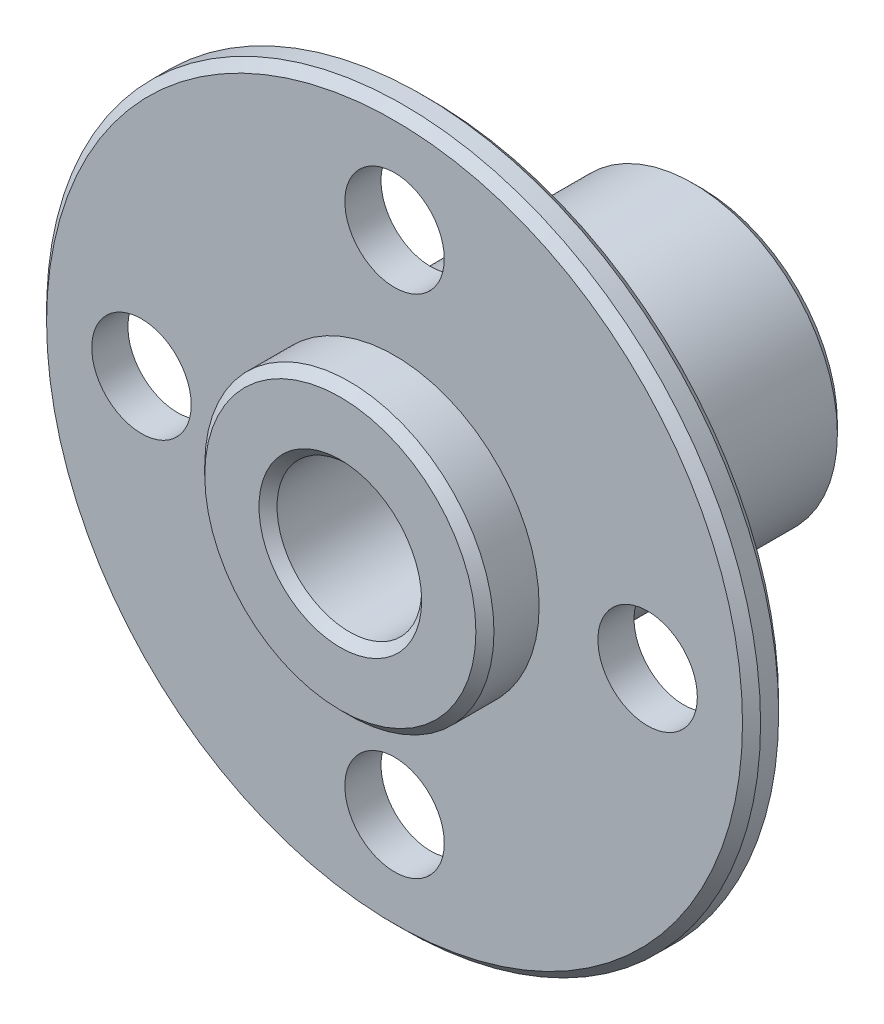
SolidWorks part; units mm, degrees
ref_plane "前视基准面" through (0, 0, 0) normal (0, 0, 1) x (1, 0, 0)
ref_plane "上视基准面" through (0, 0, 0) normal (0, 1, 0) x (1, 0, 0)
ref_plane "右视基准面" through (0, 0, 0) normal (1, 0, 0) x (0, 0, -1)
sketch "草图1" plane through (0, 0, 0) normal (0, 0, 1) x (1, 0, 0)
  circle A0 centre (0, 0) radius 19.75
  dimension "D1" = 39.5
extrude "凸台-拉伸1" add sketch "草图1" along normal blind 2
sketch "草图2" plane through (0, 0, 2) normal (0, 0, 1) x (1, 0, 0)
  circle A0 centre (0, 0) radius 8
  dimension "D1" = 16
extrude "凸台-拉伸2" add sketch "草图2" along normal blind 3
sketch "草图3" plane through (0, 0, 0) normal (0, 0, -1) x (-1, 0, 0)
  circle A0 centre (0, 0) radius 8
  dimension "D1" = 16
extrude "凸台-拉伸3" add sketch "草图3" along normal blind 15
hole_wizard "M8 螺纹孔1" positions "草图5" profile "草图4" tap size "M8" standard "GB" end condition up to next
sketch "草图5" plane through (0, 0, 5) normal (0, 0, 1) x (1, 0, 0)
  point P0 (0, 0)
sketch "草图4" plane through (0, 0, 5) normal (1, 0, 0) x (0, -1, 0)
  line L0 (0, 0) -> (0, 20)
  line L1 (0, 20) -> (4, 20)
  line L2 (4, 20) -> (4, 0)
  line L5 (4, 0) -> (0, 0)
  line L11 (0, -6.35) -> (0, 107.95) construction
  dimension "螺纹线主直径" = 8
  dimension "通孔螺纹孔钻头深度" = 20
hole_wizard "Ø5.5 (5.5) 直径孔1" positions "草图7" profile "草图6" hole size "Ø5.5" standard "GB" end condition up to next
sketch "草图7" plane through (0, 0, 2) normal (0, 0, 1) x (1, 0, 0)
  line L0 (0, 0) -> (0, 23.029) construction
  line L2 (0, 0) -> (0, -23.241) construction
  line L5 (-23.9824, 0) -> (0, 0) construction
  line L7 (0, 0) -> (25.8377, 0) construction
  circle A0 centre (0, 0) radius 14 construction
  point P0 (0, 14)
  point P1 (0, -14)
  point P3 (-14, 0)
  point P5 (14, 0)
  dimension "D1" = 28
sketch "草图6" plane through (0, 14, 2) normal (1, 0, 0) x (0, -1, 0)
  line L0 (0, 0) -> (0, 2)
  line L1 (0, 2) -> (2.75, 2)
  line L2 (2.75, 2) -> (2.75, 0)
  line L5 (2.75, 0) -> (0, 0)
  line L11 (0, -6.35) -> (0, 107.95) construction
  dimension "通孔孔直径" = 5.5
  dimension "通孔孔深度" = 2
chamfer "倒角1" distance 0.5 angle 45 6 edges at (-4, 0, -15) (-8, 0, -15) (19.75, 0, 0) (19.75, 0, 2) (4, 0, 5) (8, 0, 5)
